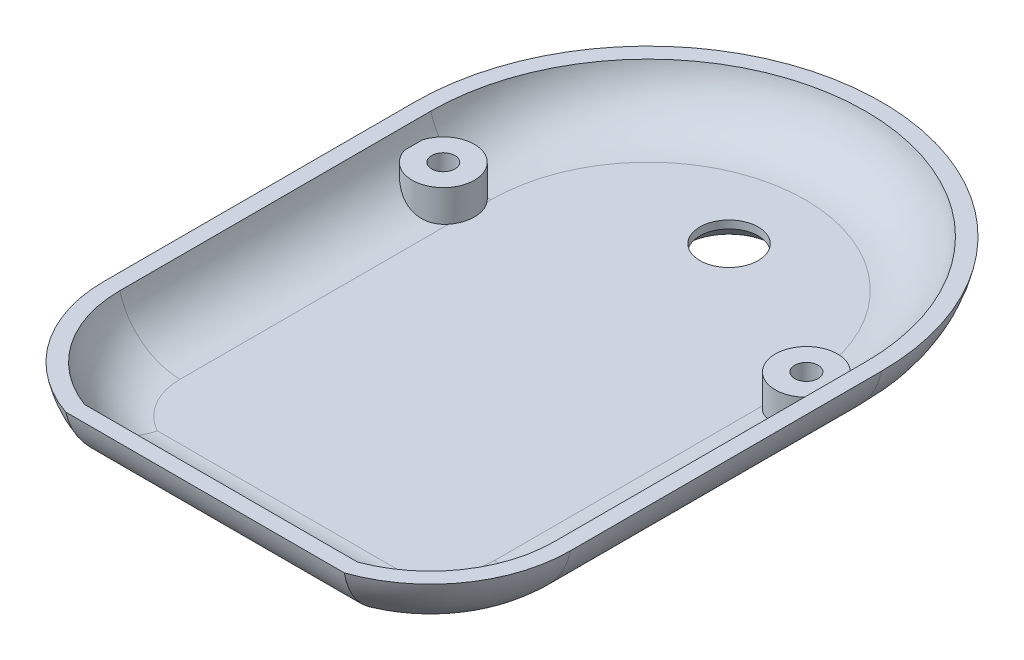
SolidWorks part; units mm, degrees
ref_plane "前视基准面" through (0, 0, 0) normal (0, 0, 1) x (1, 0, 0)
ref_plane "上视基准面" through (0, 0, 0) normal (0, 1, 0) x (1, 0, 0)
ref_plane "右视基准面" through (0, 0, 0) normal (1, 0, 0) x (0, 0, -1)
sketch "草图1" plane through (0, 0, 0) normal (0, 1, 0) x (1, 0, 0)
  line L0 (2.2835, 50) -> (2.2835, -37.4016) construction
  line L2 (-27.7165, 33.4646) -> (-27.7165, -6.5354)
  line L4 (32.2835, 33.4646) -> (32.2835, -6.5354)
  line L5 (-15.6326, -23.5354) -> (20.1995, -23.5354)
  arc A0 (32.2835, 33.4646) -> (-27.7165, 33.4646) centre (2.2835, 33.4646) ccw
  arc A1 (-27.7165, -6.5354) -> (-15.6326, -23.5354) centre (-9.7165, -6.5354) ccw
  arc A2 (32.2835, -6.5354) -> (20.1995, -23.5354) centre (14.2835, -6.5354) cw
  dimension "D1" = 60
  dimension "D2" = 40
  dimension "D3" = 18
  dimension "D4" = 17
extrude "凸台-拉伸1" add sketch "草图1" along normal blind 8
fillet "圆角1" radius 10 6 edges at (-27.7165, 0, -13.4646) (-24.3878, 0, 16.964) (2.2835, 0, 23.5354) (28.9547, 0, 16.964) (32.2835, 0, -13.4646) (2.2835, 0, -63.4646)
shell "抽壳2" thickness 2 removed face at (2.2835, 8, -5.4884)
ref_plane "基准面1" through (0, 6.1, 0) normal (0, 1, 0) x (1, 0, 0)
sketch "草图2" plane through (0, 6.1, 0) normal (0, 1, 0) x (1, 0, 0)
  line L0 (-42.6212, 33.4646) -> (45.9647, 33.4646) construction
  line L1 (2.2835, 70.1363) -> (2.2835, -31.2827) construction
  line L2 (-27.7165, 33.4646) -> (-27.7165, -6.5354) construction
  line L3 (32.2835, -6.5354) -> (32.2835, 33.4646) construction
  circle A0 centre (-21.0665, 30.4646) radius 1.5
  circle A1 centre (-21.0665, 30.4646) radius 4
  circle A2 centre (25.6335, 30.4646) radius 1.5
  circle A3 centre (25.6335, 30.4646) radius 4
  dimension "D1" = 3
  dimension "D2" = 3
  dimension "D3" = 8
  dimension "D4" = 46.7
extrude "凸台-拉伸2" add sketch "草图2" against normal up to body separate body
sketch "草图3" plane through (0, 0, 0) normal (0, 1, 0) x (1, 0, 0)
  line L0 (2.2835, 69.5134) -> (2.2835, -32.0302) construction
  line L3 (32.2835, -6.5354) -> (32.2835, 33.4646) construction
  line L4 (-27.7165, 33.4646) -> (-27.7165, -6.5354) construction
  circle A0 centre (2.2835, 43.8646) radius 7
  circle A1 centre (-21.0665, 30.4646) radius 1.5 construction
  dimension "D1" = 13.4
  dimension "D2" = 14
extrude "凸台-拉伸5" add sketch "草图3" against normal blind 1
sketch "草图5" plane through (0, 2, -2) normal (0, 1, 0) x (-1, 0, 0)
  line L0 (-2.2835, 10.5842) -> (-2.2835, -90.9594) construction
  line L1 (27.7165, -31.4646) -> (27.7165, 8.5354) construction
  line L2 (-32.2835, 8.5354) -> (-32.2835, -31.4646) construction
  circle A0 centre (-2.2835, -41.8646) radius 3.75
  circle A3 centre (-25.6335, -28.4646) radius 1.5 construction
  point P4 (-1.3076, -38.6548)
  dimension "D1" = 13.4
  dimension "D2" = 7.5
extrude "切除-拉伸2" cut sketch "草图5" against normal through all and the other way through all
chamfer "倒角3" distance 2 angle 45 1 edges at (2.2835, -1, -40.1146)
